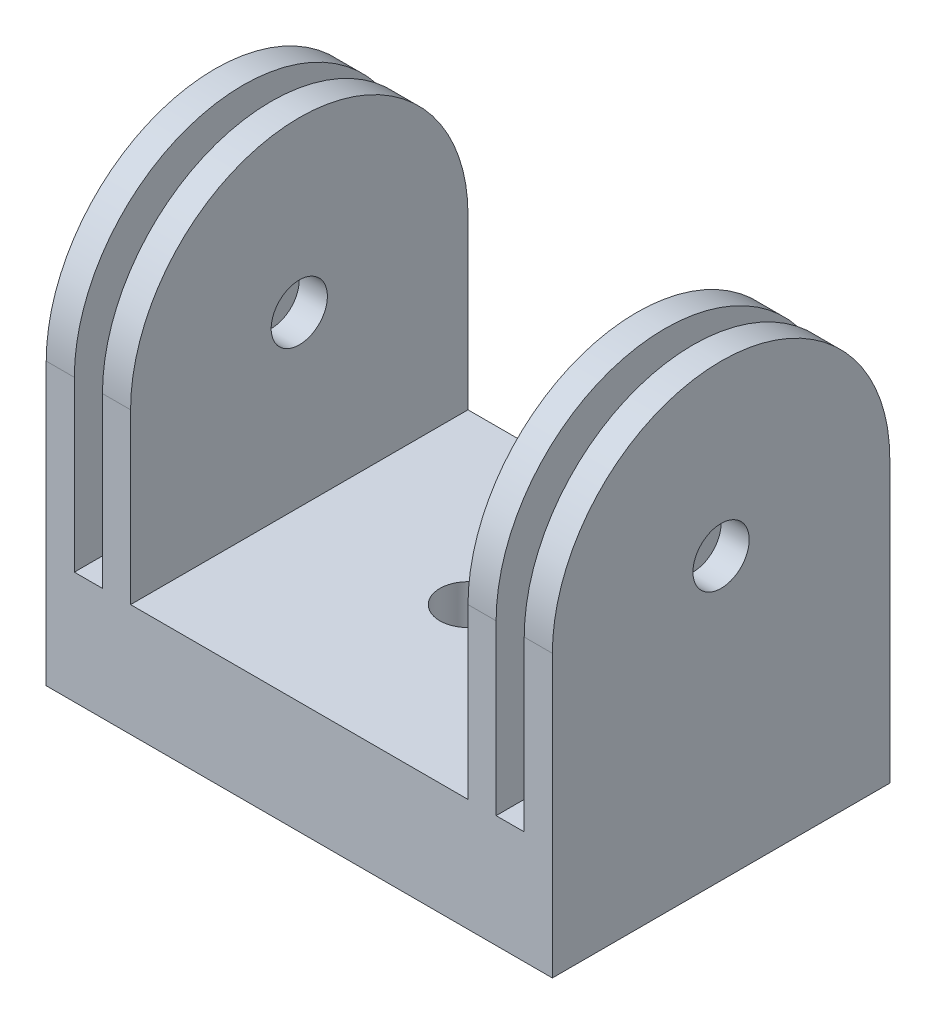
SolidWorks part; units mm, degrees
material "6061 Alloy"
ref_plane "Front Plane" through (0, 0, 0) normal (0, 0, 1) x (1, 0, 0)
ref_plane "Top Plane" through (0, 0, 0) normal (0, 1, 0) x (1, 0, 0)
ref_plane "Right Plane" through (0, 0, 0) normal (1, 0, 0) x (0, 0, -1)
sketch "Sketch1" plane through (0, 0, 0) normal (0, 1, 0) x (1, 0, 0)
  line L1 (-22.5, 15) -> (22.5, 15)
  line L2 (-22.5, 15) -> (-22.5, -15)
  line L3 (-22.5, -15) -> (22.5, -15)
  line L4 (22.5, 15) -> (22.5, -15)
  line L5 (0, -15) -> (0, 15) construction
  line L6 (-22.5, 0) -> (22.5, 0) construction
  circle A0 centre (0, 0) radius 2.5
  point P0 (0, 0)
  dimension "D1" = 45
  dimension "D3" = 5
  dimension "D2" = 30
extrude "Boss-Extrude1" add sketch "Sketch1" along normal blind 10 contours L4 L1 L2 L3 A0
sketch "Sketch2" plane through (22.5, 0, 0) normal (1, 0, 0) x (0, 0, -1)
  line L0 (15, 10) -> (15, 0) construction
  line L1 (-15, 10) -> (15, 10)
  line L2 (-15, 10) -> (-15, 25)
  line L4 (15, 10) -> (15, 25)
  arc A0 (-15, 25) -> (15, 25) centre (0, 25) cw
  circle A1 centre (0, 25) radius 2.5
  dimension "D2" = 5
  dimension "D4" = 15
  dimension "D1" = 15
  dimension "D3" = 10
extrude "Boss-Extrude2" add sketch "Sketch2" against normal blind 2.5
ref_plane "Plane1" through (18.75, 0, 0) normal (1, 0, 0) x (0, 0, -1)
mirror "Mirror2" about plane through (18.75, 0, 0) normal (1, 0, 0) of "Boss-Extrude2"
mirror "Mirror3" about plane through (0, 0, 0) normal (1, 0, 0) of "Mirror2"
